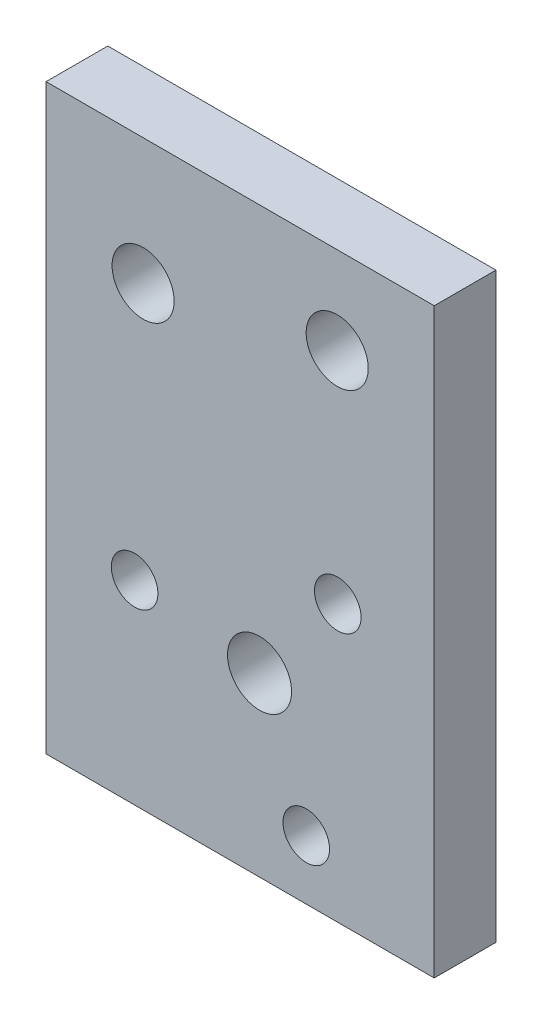
SolidWorks part; units mm, degrees
ref_plane "Front Plane" through (0, 0, 0) normal (0, 0, 1) x (1, 0, 0)
ref_plane "Top Plane" through (0, 0, 0) normal (0, 1, 0) x (1, 0, 0)
ref_plane "Right Plane" through (0, 0, 0) normal (1, 0, 0) x (0, 0, -1)
sketch "Sketch1" plane through (0, 0, 0) normal (0, 0, 1) x (1, 0, 0)
  line L1 (0, 0) -> (20, 0)
  line L2 (0, 0) -> (0, 30)
  line L3 (0, 30) -> (20, 30)
  line L4 (20, 0) -> (20, 30)
  circle A0 centre (5, 23.5) radius 1.6
  circle A1 centre (15, 25.5) radius 1.6
  circle A10 centre (15.03, 14.205) radius 1.2
  circle A11 centre (13.4076, 3.0548) radius 1.2
  circle A12 centre (4.5624, 10.035) radius 1.2
  circle A13 centre (11, 9.0982) radius 1.65
  point P17 (11, 9.0982)
  point P18 (-6.5239, 10.8325)
  dimension "D7" = 3.2
  dimension "D8" = 3.2
  dimension "D9" = 4.97
  dimension "D10" = 3
  dimension "D11" = 9
  dimension "D12" = 4.17
  dimension "D1" = 20
  dimension "D2" = 30
  dimension "D3" = 6.5
  dimension "D4" = 4.5
  dimension "D5" = 5
  dimension "D6" = 5
extrude "Boss-Extrude3" add sketch "Sketch1" along normal blind 3.18
